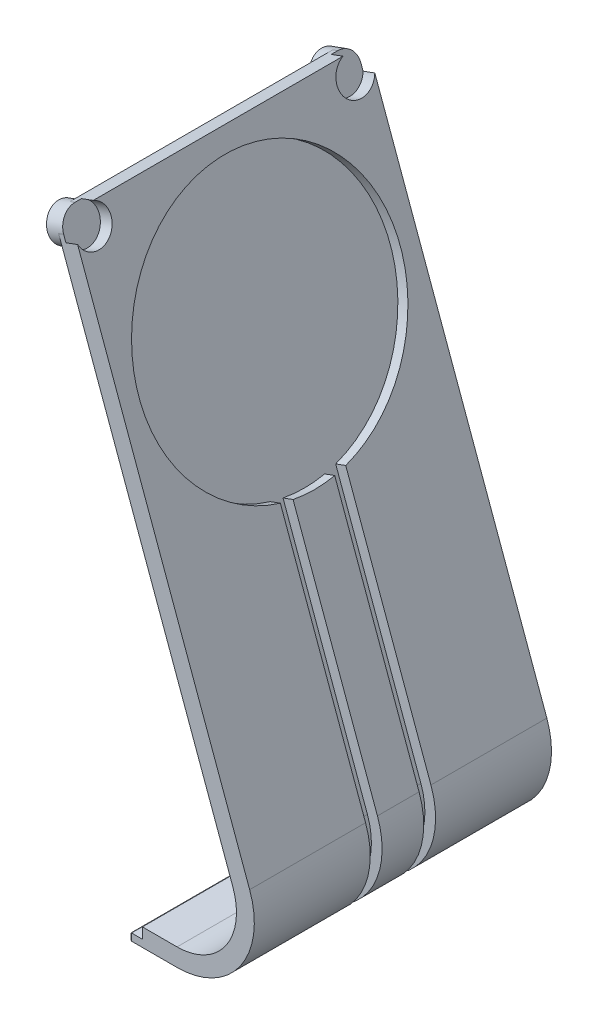
SolidWorks part; units mm, degrees
material "PLA"
ref_plane "前视基准面" through (0, 0, 0) normal (0, 0, 1) x (1, 0, 0)
ref_plane "上视基准面" through (0, 0, 0) normal (0, 1, 0) x (1, 0, 0)
ref_plane "右视基准面" through (0, 0, 0) normal (1, 0, 0) x (0, 0, -1)
other "Configuration Table"
sketch "草图2" plane through (0, 0, 0) normal (0, 0, 1) x (1, 0, 0)
  line L0 (27.4812, 0) -> (33.3109, 0)
  line L5 (42.7078, 13.4202) -> (12.3985, 96.6944)
  line L6 (42.7078, 13.4202) -> (9.2861, 105.2456) construction
  line L8 (33.3109, 0) -> (33.3109, -1) construction
  line L9 (-42.6188, 0) -> (33.3109, 0) construction
  line L10 (15.2773, 97.8486) -> (12.3643, 96.7883) construction
  line L11 (-42.6188, 0) -> (33.3109, 0) construction
  line L13 (27.3812, 0) -> (27.3812, -1.7) construction
  arc A0 (33.3109, 0) -> (42.7078, 13.4202) centre (33.3109, 10) ccw
  dimension "D3" = 0.1
  dimension "D2" = 10
  dimension "D1" = 0.1
extrude "整体拉伸-薄壁1" add sketch "草图2" along normal mid plane 50 thin thin type one direction wall 3
sketch "草图4" plane through (44.8442, 16.3219, 0) normal (0.9397, 0.342, 0) x (0, 0, -1)
  line L0 (-25, 86.6225) -> (25, 86.6225) construction
  circle A0 centre (0, 61.2225) radius 22
  dimension "D1" = 44
  dimension "D2" = 25.4
extrude "中间圆切除-拉伸1" cut sketch "草图4" against normal blind 1.8
sketch "草图3" plane through (0, 0, 0) normal (0, 0, 1) x (1, 0, 0)
  line L0 (45.5269, 14.4463) -> (15.2176, 97.7204) construction
  line L1 (45.5269, 14.4463) -> (15.2176, 97.7204) construction
  line L2 (27.4812, -3) -> (33.3109, -3) construction
  line L3 (27.4812, -3) -> (33.3109, -3) construction
  line L4 (8.763, -1.2) -> (33.3109, -1.2)
  line L5 (43.8354, 13.8306) -> (29.7379, 52.5634)
  line L6 (43.8354, 13.8306) -> (13.5261, 97.1048) construction
  line L7 (27.4812, -1.2) -> (33.3109, -1.2) construction
  line L9 (29.7379, 52.5634) -> (31.4293, 53.179) construction
  line L16 (29.7379, 52.5634) -> (28.7118, 55.3824)
  arc A0 (33.3109, 0) -> (42.7078, 13.4202) centre (33.3109, 10) ccw construction
  arc A1 (33.3109, -3) -> (45.5269, 14.4463) centre (33.3109, 10) ccw construction
  arc A2 (33.3109, -1.2) -> (43.8354, 13.8306) centre (33.3109, 10) ccw
  dimension "D2" = 3
  dimension "D1" = 1.8
extrude "线槽切除-拉伸-薄壁1" cut sketch "草图3" against normal blind 2 from offset 5.5 thin thin type one direction wall 1.8
mirror "镜向1" about plane through (0, 0, 0) normal (0, 0, 1) of "线槽切除-拉伸-薄壁1"
sketch "草图6" plane through (27.4812, 0, 0) normal (-1, 0, 0) x (0, 0, 1)
  line L1 (-25, -1.8) -> (-5.5, -1.8)
  line L2 (-25, -1.8) -> (-25, -3)
  line L3 (-25, -3) -> (-5.5, -3)
  line L4 (-5.5, -1.8) -> (-5.5, -3)
  line L6 (5.5, -1.8) -> (25, -1.8)
  line L7 (5.5, -1.8) -> (5.5, -3)
  line L8 (5.5, -3) -> (25, -3)
  line L9 (25, -1.8) -> (25, -3)
  line L10 (-25, -3) -> (-25, 0) construction
  line L12 (5.5, -3) -> (5.5, -1.2) construction
  dimension "D1" = 1.2
extrude "凸台-拉伸1" add sketch "草图6" along normal blind 2
fillet "圆角1" radius 0.2 9 edges at (25.4812, -1.8, 15.25) (25.4812, -2.4, 25) (25.4812, -3, 15.25) (25.4812, -2.4, 5.5) (25.4812, -1.8, -15.25) (25.4812, -2.4, -5.5) (25.4812, -3, -15.25) (25.4812, -2.4, -25) (27.4812, -3, 0)
sketch "草图7" plane through (42.0251, 15.2959, 0) normal (-0.9397, -0.342, 0) x (0, 0, 1)
  line L0 (25, 86.6225) -> (-25, 86.6225) construction
  line L3 (0, 86.6225) -> (0, 71.6076) construction
  circle A0 centre (-22.1, 83.7225) radius 1
  circle A1 centre (-22.1, 83.7225) radius 2.9
  circle A2 centre (22.1, 83.7225) radius 2.9
  circle A3 centre (22.1, 83.7225) radius 1
  dimension "D1" = 2
extrude "凸台-拉伸2" add sketch "草图7" along normal blind 2
sketch "草图8" plane through (42.0251, 15.2959, 0) normal (-0.9397, -0.342, 0) x (0, 0, 1)
  line L0 (0, 86.6225) -> (0, 70.5485) construction
  line L1 (-26.1984, 87.8209) -> (-22.1984, 87.8209)
  line L2 (-26.1984, 87.8209) -> (-26.1984, 83.8209)
  line L3 (-26.1984, 83.8209) -> (-25.1984, 83.8209)
  line L4 (-22.1984, 87.8209) -> (-22.1984, 86.8209)
  line L5 (22.1, 86.6225) -> (-22.1, 86.6225) construction
  line L6 (22.1984, 87.8209) -> (22.1984, 86.8209)
  line L7 (26.1984, 83.8209) -> (25.1984, 83.8209)
  line L8 (26.1984, 87.8209) -> (26.1984, 83.8209)
  line L9 (26.1984, 87.8209) -> (22.1984, 87.8209)
  arc A0 (-25.1984, 83.8209) -> (-22.1984, 86.8209) centre (-22.1, 83.7225) ccw
  arc A1 (-25.1, 83.7225) -> (-22.1, 86.7225) centre (-22.1, 83.7225) ccw construction
  arc A2 (25.1984, 83.8209) -> (22.1984, 86.8209) centre (22.1, 83.7225) cw
  dimension "D1" = 0.1
  dimension "D2" = 4
  dimension "D3" = 4
  dimension "D4" = 1
  dimension "D5" = 1
extrude "切除-拉伸1" cut sketch "草图8" along normal blind 2.1 from surface starting at face at (32.5142, 50.1984, 0)
sketch "草图9" plane through (42.0251, 15.2959, 0) normal (-0.9397, -0.342, 0) x (0, 0, 1)
  line L0 (-22.1, 86.6225) -> (-25, 86.6225) construction
  line L1 (-22.1, 86.6225) -> (-25, 86.6225)
  line L2 (-25, 83.7225) -> (-25, 86.6225) construction
  line L3 (-25, 83.7225) -> (-25, 86.6225)
  line L4 (0, 86.6225) -> (0, 58.5215) construction
  line L5 (22.1, 86.6225) -> (-22.1, 86.6225) construction
  line L6 (25, 83.7225) -> (25, 86.6225)
  line L7 (22.1, 86.6225) -> (25, 86.6225)
  circle A0 centre (-22.1, 83.7225) radius 2.9 construction
  arc A1 (-22.1, 86.6225) -> (-25, 83.7225) centre (-22.1, 83.7225) ccw
  arc A2 (22.1, 86.6225) -> (25, 83.7225) centre (22.1, 83.7225) cw
extrude "切除-拉伸2" cut sketch "草图9" against normal up to next
